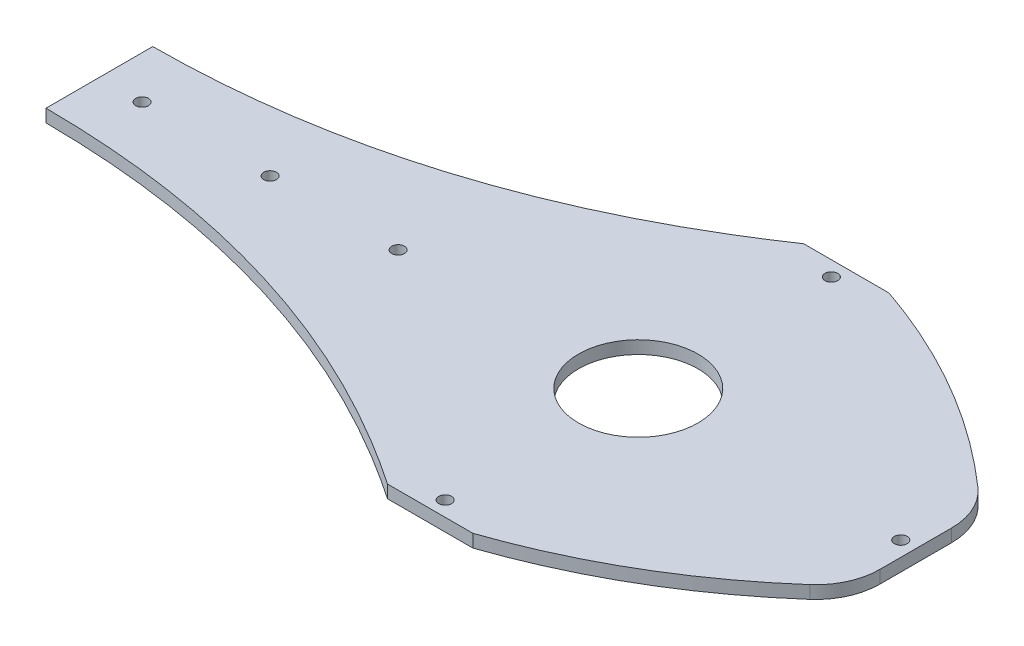
SolidWorks part; units mm, degrees
material "Thornel Mat VMA"
ref_plane "Front Plane" through (0, 0, 0) normal (0, 0, 1) x (1, 0, 0)
ref_plane "Top Plane" through (0, 0, 0) normal (0, 1, 0) x (1, 0, 0)
ref_plane "Right Plane" through (0, 0, 0) normal (1, 0, 0) x (0, 0, -1)
sketch "Sketch1" plane through (0, 0, 0) normal (0, 1, 0) x (1, 0, 0)
  line L0 (0, 0) -> (0, 48.75)
  line L1 (0, 0) -> (65, 0)
  line L2 (65, 0) -> (65, 15)
  line L3 (32.5, 0) -> (10, 48.75)
  line L4 (21.25, 24.375) -> (21.25, 44.375)
  line L5 (0, 48.75) -> (10, 48.75)
  spline S0 degree 2 poles (65, 15) (40.7961, 38.1894) (10, 48.75) knots 0 0 0 1 1 1
  point P3 (32.5, 0)
  dimension "D1" = 48.75
  dimension "D2" = 65
  dimension "D3" = 15
  dimension "D4" = 20
  dimension "D5" = 10
extrude "Boss-Extrude1" add sketch "Sketch1" against normal blind 1.5 and the other way blind 1.5 contours L1 L0 | L2 L1 | L4 S0 L3 region at (11.6176, 0, -20.0735) region at (41.3852, 0, -17.8863) region at (17.4839, 0, -39.2315)
sketch "Sketch2" plane through (0, 1.5, 0) normal (0, 1, 0) x (1, 0, 0)
  line L1 (0, 0) -> (0, 48.75) construction
  line L2 (65, 0) -> (61.5, 0)
  line L3 (0, 0) -> (65, 0) construction
  circle A0 centre (0, 45.25) radius 1.5
  circle A1 centre (61.5, 0) radius 1.5
  dimension "D2" = 3
  dimension "D4" = 3
  dimension "D3" = 3.5
extrude "Cut-Extrude1" cut sketch "Sketch2" against normal through all contours A0 | A1
fillet "Fillet1" radius 15 1 edges at (65, 0, -15) type face fillet first side face at (65, 0, -7.5) second side face at (51.25, 0, -23.4375)
mirror "Mirror2" about plane through (0, 0, 0) normal (0, 0, 1) of "Fillet1", "Boss-Extrude1", "Cut-Extrude1"
sketch "Sketch3" plane through (0, 0, 0) normal (0, 1, 0) x (1, 0, 0)
  line L0 (0, 0) -> (-46.25, 0)
  line L1 (-46.25, 0) -> (-56.25, 0)
  line L2 (-56.25, 0) -> (-86.25, 0)
  line L3 (-86.25, 0) -> (-116.25, 0)
  line L4 (-116.25, 0) -> (-126.25, 0)
  line L5 (0, 48.75) -> (-10, 48.75)
  line L6 (-126.25, 0) -> (-126.25, 12.5)
  line L7 (-71.25, 0) -> (-71.25, 20)
  line L8 (0, 46.75) -> (0, 48.75)
  line L9 (0, 43.75) -> (0, 0)
  circle A0 centre (-116.25, 0) radius 1.5
  circle A1 centre (-86.25, 0) radius 1.5
  circle A2 centre (-56.25, 0) radius 1.5
  circle A3 centre (0, 45.25) radius 1.5
  spline S0 degree 2 poles (-126.25, 12.5) (-62.8537, 12.7779) (-10, 48.75) knots 0 0 0 1 1 1
  dimension "D6" = 3
  dimension "D7" = 3
  dimension "D8" = 3
  dimension "D12" = 3
  dimension "D1" = 46.25
  dimension "D2" = 10
  dimension "D3" = 30
  dimension "D4" = 30
  dimension "D5" = 10
  dimension "D9" = 10
  dimension "D10" = 12.5
  dimension "D11" = 20
extrude "Boss-Extrude2" add sketch "Sketch3" along normal blind 1.5 and the other way blind 1.5 contours S0 L7 L2 A2 L1 L0 L9 A3 L5 | S0 L6 L4 A0 L3 A1 L2 L7 region at (-29.9657, 0, -18.6325) region at (-96.4339, 0, -7.7217)
mirror "Mirror3" about plane through (0, 0, 0) normal (0, 0, 1) of "Boss-Extrude2"
sketch "Sketch4" plane through (0, 1.5, 0) normal (0, 1, 0) x (1, 0, 0)
  line L0 (0, 45.25) -> (0, -45.25)
  circle A0 centre (0, 0) radius 14
  dimension "D1" = 28
extrude "Cut-Extrude2" cut sketch "Sketch4" against normal through all contours L0 A0 | L0 A0 region at (5.9418, 1.5, 0) region at (-5.9418, 1.5, 0)
